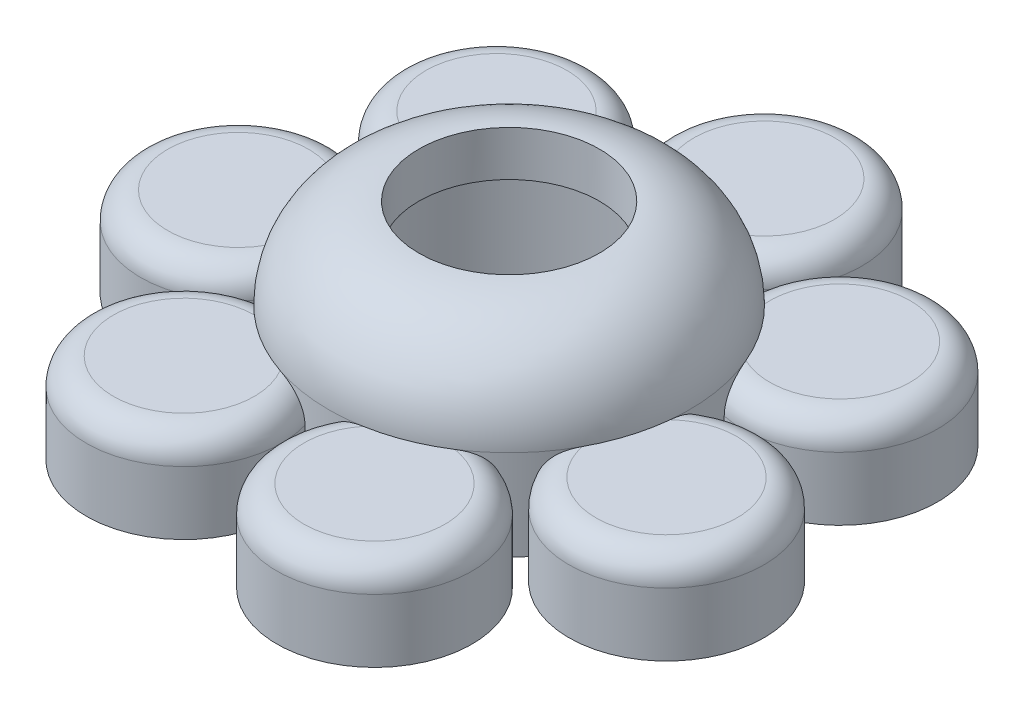
SolidWorks part; units mm, degrees
ref_plane "Front Plane" through (0, 0, 0) normal (0, 0, 1) x (1, 0, 0)
ref_plane "Top Plane" through (0, 0, 0) normal (0, 1, 0) x (1, 0, 0)
ref_plane "Right Plane" through (0, 0, 0) normal (1, 0, 0) x (0, 0, -1)
sketch "Sketch3" plane through (0, 0, 0) normal (0, 1, 0) x (1, 0, 0)
  circle A0 centre (0, 0) radius 20
extrude "Boss-Extrude2" add sketch "Sketch3" along normal blind 20 contours A0
fillet "Fillet2" radius 10 1 edges at (0, 20, 20)
sketch "Sketch4" plane through (0, 20, 0) normal (0, 1, 0) x (1, 0, 0)
  circle A0 centre (0, 0) radius 10
extrude "Cut-Extrude1" cut sketch "Sketch4" against normal through all
sketch "Sketch5" plane through (0, 0, 0) normal (0, -1, 0) x (1, 0, 0)
  circle A2 centre (0, 0) radius 17
  circle A3 centre (0, 0) radius 17
  dimension "D1" = 3
extrude "Cut-Extrude3" cut sketch "Sketch5" against normal blind 15
sketch "Sketch6" plane through (0, 0, 0) normal (0, -1, 0) x (1, 0, 0)
  arc A0 (-19.4613, -4.6107) -> (-17.2345, 10.1474) centre (-26.0774, 3.9346) cw
  circle A1 centre (0, 0) radius 20 construction
  arc A2 (-15.7387, 12.3407) -> (-2.812, 19.8013) centre (-13.1828, 22.8414) cw
  arc A3 (-0.1645, 19.9993) -> (13.7281, 14.5444) centre (9.6388, 24.5481) cw
  arc A4 (15.5335, 12.598) -> (19.9306, -1.6647) centre (25.2021, 7.7696) cw
  arc A5 (19.5345, -4.2899) -> (11.125, -16.6203) centre (21.7878, -14.8596) cw
  arc A6 (8.8256, -17.9474) -> (-6.058, -19.0605) centre (1.9668, -26.2991) cw
  arc A7 (-8.5292, -18.0902) -> (-18.6791, -7.1477) centre (-19.3352, -17.9349) cw
  point P26 (0, 0)
  circle M2 centre (0, 0) radius 20
  dimension "D1" = 7
extrude "Boss-Extrude3" add sketch "Sketch6" against normal blind 10 contours A5 M2 | A4 M2 | A3 M2 | A2 M2 | A0 M2 | A7 M2 | A6 M2 region at (-27.2509, 0, 4.1117) region at (-20.2053, 0, -18.742) region at (-13.776, 0, 23.8692) region at (2.0553, 0, -27.4826) region at (10.0725, 0, 25.6527) region at (22.7682, 0, -15.5282) region at (26.3362, 0, 8.1192)
fillet "Fillet4" radius 3 7 edges at (-36.7637, 10, 5.547) (-27.2586, 10, -25.2845) (2.7727, 10, -37.0762) (30.7162, 10, -20.9488) (35.5297, 10, 10.9535) (13.5886, 10, 34.6076) (-18.5849, 10, 32.2015)
sketch "Sketch7" plane through (0, 0, 0) normal (0, -1, 0) x (-1, 0, 0)
  line L0 (-2.7727, 37.0762) -> (-53.5154, 17.6162) construction
  arc A0 (6.058, 19.0605) -> (-8.8256, 17.9474) centre (-1.9668, 26.2991) ccw construction
